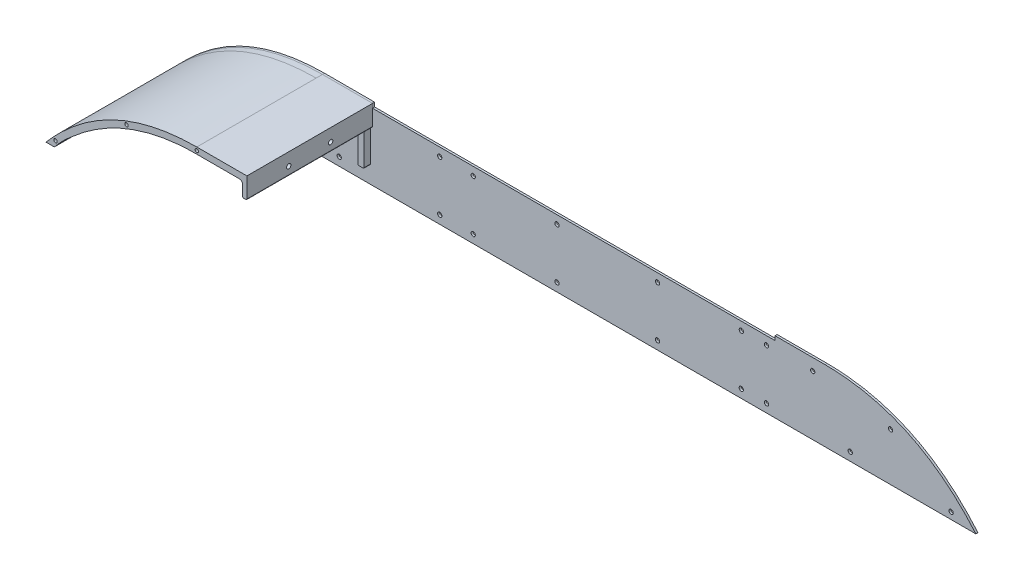
SolidWorks part; units mm, degrees
ref_plane "Front Plane" through (0, 0, 0) normal (0, 0, 1) x (1, 0, 0)
ref_plane "Top Plane" through (0, 0, 0) normal (0, 1, 0) x (1, 0, 0)
ref_plane "Right Plane" through (0, 0, 0) normal (1, 0, 0) x (0, 0, -1)
sketch "Sketch1" plane through (0, 0, 0) normal (0, 0, 1) x (1, 0, 0)
  line L0 (0, 0) -> (-304.8, 0)
  line L1 (0, 0) -> (609.6, 0)
  line L2 (0, 0) -> (0, 107.95) construction
  line L3 (0, 107.95) -> (609.6, 107.95)
  line L4 (609.6, 0) -> (609.6, 107.95) construction
  line L5 (609.6, 0) -> (914.4, 0)
  line L6 (304.8, -1000) -> (304.8, 49000) construction
  line L7 (0, 107.95) -> (-76.2, 107.95)
  line L8 (609.6, 107.95) -> (685.8, 107.95)
  spline S0 degree 2 poles (-304.8, 0) (-213.404, 107.36) (-76.2, 107.95) knots 0 0 0 1 1 1
  spline S1 degree 2 poles (914.4, 0) (823.004, 107.36) (685.8, 107.95) knots 0 0 0 1 1 1
  point P11 (304.8, 0)
  dimension "D1" = 609.6
  dimension "D2" = 107.95
  dimension "D3" = 304.8
  dimension "D4" = 76.2
extrude "Boss-Extrude1" add sketch "Sketch1" along normal blind 3.175
sketch "Sketch2" plane through (0, 0, 3.175) normal (0, 0, 1) x (1, 0, 0)
  line L8 (685.8, 107.95) -> (-76.2, 107.95) construction
  line L11 (0, 107.95) -> (609.6, 107.95)
  line L12 (0, 107.95) -> (0, 101.6) construction
  line L13 (0, 101.6) -> (609.6, 101.6)
  line L14 (609.6, 107.95) -> (609.6, 101.6) construction
  line L15 (-0.254, 107.95) -> (-0.254, 101.6)
  line L16 (609.854, 107.95) -> (609.854, 101.6)
  line L19 (609.6, 107.95) -> (609.854, 107.95)
  line L20 (609.6, 101.6) -> (609.854, 101.6)
  line L21 (-0.254, 107.95) -> (0, 107.95)
  line L22 (-0.254, 101.6) -> (0, 101.6)
  dimension "D1" = 609.6
  dimension "D2" = 6.35
  dimension "D3" = 0.254
  dimension "D4" = 0.254
extrude "Cut-Extrude1" cut sketch "Sketch2" against normal through all
sketch "Sketch3" plane through (0, 0, 3.175) normal (0, 0, 1) x (1, 0, 0)
  line L5 (-76.0908, 82.5502) -> (-76.2, 107.95) construction
  line L6 (685.8, 107.95) -> (609.854, 107.95)
  line L7 (609.854, 107.95) -> (609.854, 101.6)
  line L8 (609.854, 101.6) -> (-0.254, 101.6)
  line L9 (-0.254, 101.6) -> (-0.254, 107.95)
  line L10 (-0.254, 107.95) -> (-76.2, 107.95)
  line L11 (-304.8, 0) -> (914.4, 0)
  line L19 (-304.8, 0) -> (-254.508, 0)
  line L20 (-304.8, 0) -> (914.4, 0) construction
  line L21 (-254.508, 0) -> (-254.508, 15.3448)
  line L22 (-76.2, 107.95) -> (-0.254, 107.95)
  line L23 (-0.254, 107.95) -> (-0.254, 76.2)
  line L24 (-0.254, 76.2) -> (-6.604, 76.2)
  line L25 (-6.604, 76.2) -> (-6.604, 82.5502)
  line L26 (-6.604, 82.5502) -> (-76.0908, 82.5502)
  parabola Q2 (-76.2, 107.95) -> (-304.8, 0) focus (-138.8032, -41.5009) apex (-192.9562, 84.7198)
  parabola Q3 (914.4, 0) -> (685.8, 107.95) focus (748.4032, -41.5009) apex (802.5562, 84.7198)
  parabola Q4 (-76.2, 107.95) -> (-304.8, 0) focus (-138.8032, -41.5009) apex (-192.9562, 84.7198)
  spline S0 degree 1 poles (-76.0908, 82.5502) (-285.4592, -16.4649) knots 0 0 1 1 construction
  spline S1 degree 3 poles (-76.0908, 82.5502) (-78.7263, 82.5389) (-84.0207, 82.4515) (-94.414, 82.0204) (-107.175, 81.0024) (-122.0857, 79.0209) (-140.2937, 75.5918) (-157.8592, 70.8643) (-175.9104, 64.4537) (-194.5198, 56.4637) (-212.4049, 46.7322) (-228.6865, 35.996) (-240.414, 27.3) (-249.9299, 19.4397) (-257.5609, 12.6326) (-263.3873, 7.1473) (-268.2089, 2.3627) (-271.8925, -1.4301) (-275.5622, -5.3024) (-280.0978, -10.2646) (-283.6939, -14.3913) (-285.4592, -16.4649) knots 0.497516 0.497516 0.497516 0.497516 0.497684 0.497853 0.498189 0.498526 0.498863 0.499456 0.499793 0.50021 0.500884 0.501221 0.501558 0.501878 0.502046 0.502231 0.502399 0.502483 0.502568 0.502737 0.502905 0.502905 0.502905 0.502905 only from (-76.0908, 82.5502) to (-270.5007, 0) construction
  spline S2 degree 2 poles (-254.508, 15.3448) (-177.7983, 82.8932) (-76.0908, 82.5502) knots 0 0 0 1 1 1
  dimension "D2" = 31.75
  dimension "D3" = 6.35
  dimension "D5" = 50.292
  dimension "D1" = 0
  dimension "D4" = 25.4
extrude "Boss-Extrude2" add sketch "Sketch3" along normal blind 9.525
sketch "Sketch5" plane through (0, 0, 12.7) normal (0, 0, 1) x (1, 0, 0)
  line L7 (-304.8, 0) -> (-292.1, 0)
  line L8 (-76.0372, 98.4251) -> (-6.604, 98.4251)
  line L9 (-6.604, 98.4251) -> (-6.604, 82.5502)
  line L14 (-304.8, 0) -> (-254.508, 0)
  line L15 (-254.508, 0) -> (-254.508, 15.3448)
  line L16 (-76.0908, 82.5502) -> (-6.604, 82.5502)
  line L17 (-6.604, 82.5502) -> (-6.604, 76.2)
  line L18 (-6.604, 76.2) -> (-0.254, 76.2)
  line L19 (-0.254, 76.2) -> (-0.254, 107.95)
  line L20 (-0.254, 107.95) -> (-76.2, 107.95)
  line L24 (-6.604, 82.5502) -> (-6.604, 76.2)
  line L25 (-6.604, 76.2) -> (-0.254, 76.2)
  line L26 (-0.254, 76.2) -> (-0.254, 107.95)
  line L27 (-0.254, 107.95) -> (-76.2, 107.95)
  parabola Q4 (-76.2, 107.95) -> (-304.8, 0) focus (-138.8032, -41.5009) apex (-192.9562, 84.7198)
  parabola Q5 (-254.508, 15.3448) -> (-76.0908, 82.5502) focus (-126.3995, -51.2914) apex (-169.7975, 66.5726)
  parabola Q6 (-76.2, 107.95) -> (-304.8, 0) focus (-138.8032, -41.5009) apex (-192.9562, 84.7198)
  parabola Q7 (-254.508, 15.3448) -> (-76.0908, 82.5502) focus (-126.3995, -51.2914) apex (-169.7975, 66.5726) construction
  spline S0 degree 1 poles (-264.9993, 27.259) (-76.0372, 98.4251) knots 0 0 1 1 construction
  spline S1 degree 3 poles (-264.9993, 27.259) (-263.3249, 28.7335) (-259.9376, 31.6547) (-253.107, 37.2998) (-244.419, 44.0244) (-233.7687, 51.5472) (-219.2659, 60.8476) (-200.5783, 71.0931) (-177.2837, 81.1523) (-153.1553, 88.9561) (-132.3866, 93.5719) (-115.3933, 96.1333) (-102.4647, 97.4901) (-91.5371, 98.1519) (-82.7134, 98.4012) (-78.2591, 98.4326) (-76.0372, 98.4251) knots 0.497832 0.497832 0.497832 0.497832 0.497965 0.498098 0.498363 0.498629 0.498895 0.499427 0.499958 0.50049 0.501022 0.501287 0.501553 0.501819 0.501952 0.502085 0.502085 0.502085 0.502085
  spline S2 degree 2 poles (-264.9993, 27.259) (-280.0432, 15.0907) (-292.1, 0) knots 0 0 0 1 1 1
  dimension "D3" = 12.7
  dimension "D1" = 0
  dimension "D2" = 15.875
extrude "Boss-Extrude3" add sketch "Sketch5" along normal blind 180.975
sketch "Sketch6" plane through (0, 0, 12.7) normal (0, 0, 1) x (1, 0, 0)
  line L1 (-254.508, 0) -> (-226.4253, 0)
  line L2 (-254.508, 0) -> (-254.508, 28.575)
  line L3 (-254.508, 28.575) -> (-226.4253, 28.575)
  line L4 (-226.4253, 0) -> (-226.4253, 28.575)
  dimension "D1" = 28.575
extrude "Cut-Extrude2" cut sketch "Sketch6" against normal up to surface (9.525 mm away) up to face at (204.1979, 60.3971, 3.175)
sketch "Sketch7" plane through (0, 0, 12.7) normal (0, 0, 1) x (1, 0, 0)
  line L0 (-292.1, 0) -> (-254.508, 0) construction
  line L1 (-254.508, 0) -> (-254.508, 28.575) construction
  line L2 (-76.0651, 90.1702) -> (-9.6958, 90.1702) construction
  line L3 (-6.604, 98.4251) -> (-6.604, 76.2) construction
  circle A0 centre (-267.208, 10.16) radius 3.275
  circle A1 centre (-175.3658, 72.6223) radius 3.275
  circle A3 centre (-57.404, 90.1702) radius 3.275
  parabola Q0 (-238.3942, 28.575) -> (-76.0908, 82.5502) focus (-126.3995, -51.2914) apex (-169.7975, 66.5726) construction
  parabola Q1 (-238.3942, 28.575) -> (-76.0908, 82.5502) focus (-126.3995, -51.2914) apex (-169.7975, 66.5726) construction
  spline S0 degree 1 poles (-243.0182, 34.6317) (-76.0651, 90.1702) knots 0 0 1 1 construction
  spline S1 degree 3 poles (-243.0182, 34.6317) (-239.9935, 36.9409) (-233.8311, 41.4586) (-224.4638, 47.7679) (-214.9157, 53.6525) (-202.0674, 60.8581) (-190.551, 66.4075) (-178.8009, 71.3309) (-171.8366, 73.9914) (-159.5844, 78.2202) (-143.5556, 82.8056) (-125.3458, 86.3973) (-110.4698, 88.391) (-99.1613, 89.4468) (-89.6088, 89.961) (-81.8979, 90.1535) (-78.0064, 90.1767) (-76.0651, 90.1702) knots 0.498271 0.498271 0.498271 0.498271 0.49851 0.498748 0.498986 0.499225 0.499694 0.499813 0.500051 0.500178 0.500655 0.501131 0.50137 0.501608 0.501846 0.501966 0.502085 0.502085 0.502085 0.502085 construction
  dimension "D1" = 6.55
  dimension "D5" = 6.55
  dimension "D6" = 6.55
  dimension "D2" = 10.16
  dimension "D4" = 12.7
  dimension "D7" = 50.8
  dimension "D3" = 7.62
extrude "Cut-Extrude3" cut sketch "Sketch7" against normal through all
sketch "Sketch8" plane through (-0.254, 0, 0) normal (1, 0, 0) x (0, 0, -1)
  line L0 (-1151.3542, 88.9) -> (48848.6458, 88.9) construction
  line L1 (-193.675, 76.2) -> (-3.175, 76.2) construction
  line L2 (-3.175, 76.2) -> (-3.175, 101.6) construction
  circle A2 centre (-66.675, 88.9) radius 3.325
  circle A5 centre (-130.175, 88.9) radius 3.325
  dimension "D2" = 6.65
  dimension "D4" = 63.5
  dimension "D1" = 12.7
  dimension "D3" = 2
extrude "Cut-Extrude5" cut sketch "Sketch8" against normal up to surface (6.35 mm away) up to face at (-6.604, 85.7251, 69.85)
sketch "Sketch9" plane through (0, 0, 193.675) normal (0, 0, 1) x (1, 0, 0)
  circle A0 centre (-290.3708, 9.1426) radius 2.6
  circle A1 centre (-182.7594, 83.8165) radius 2.6
  circle A2 centre (-76.1798, 103.25) radius 2.6
  parabola Q0 (-76.2, 107.95) -> (-304.8, 0) focus (-138.8032, -41.5009) apex (-192.9562, 84.7198) construction
  parabola Q1 (-76.2, 107.95) -> (-304.8, 0) focus (-138.8032, -41.5009) apex (-192.9562, 84.7198) construction
  spline S0 degree 1 poles (-76.1798, 103.25) (-301.2212, -3.0467) knots 0 0 1 1 construction
  spline S1 degree 3 poles (-76.1798, 103.25) (-78.9851, 103.238) (-84.6167, 103.1451) (-95.7036, 102.6853) (-109.3519, 101.5971) (-125.3575, 99.4709) (-145.1456, 95.7451) (-161.7727, 91.2541) (-177.9517, 85.7316) (-188.5878, 81.5829) (-206.0869, 73.7491) (-227.5653, 62.0602) (-249.2337, 46.8941) (-265.8815, 33.1047) (-277.7275, 22.2059) (-286.3, 13.5161) (-292.1052, 7.2837) (-296.2196, 2.7435) (-299.3516, -0.8505) (-301.2212, -3.0467) knots 0.497516 0.497516 0.497516 0.497516 0.497684 0.497853 0.498189 0.498526 0.498863 0.499468 0.499636 0.499973 0.50021 0.500884 0.501558 0.501895 0.502231 0.502544 0.502628 0.502737 0.502905 0.502905 0.502905 0.502905 construction
  dimension "D2" = 5.2
  dimension "D3" = 5.2
  dimension "D4" = 5.2
  dimension "D1" = 4.7
extrude "Cut-Extrude6" cut sketch "Sketch9" against normal blind 12.7
sketch "Sketch11" plane through (-254.508, 0, 0) normal (1, 0, 0) x (0, 0, -1)
  line L0 (-3.175, 0) -> (-3.175, 28.575) construction
  line L1 (-12.7, 0) -> (-3.175, 0) construction
  circle A0 centre (-7.1374, 3.9751) radius 1.9
  circle A3 centre (-7.1374, 21.4251) radius 1.9
  dimension "D3" = 3.8
  dimension "D1" = 3.9624
  dimension "D2" = 3.9751
  dimension "D4" = 2
extrude "Boss-Extrude5" add sketch "Sketch11" along normal blind 10.16
sketch "Sketch14" plane through (0, 82.5502, 0) normal (0, -1, 0) x (1, 0, 0)
  line L5 (-76.0372, 12.7) -> (-6.604, 12.7) construction
  line L6 (-0.254, 3.175) -> (-12.954, 3.175)
  line L7 (-0.254, 3.175) -> (-0.254, 12.7)
  line L8 (-0.254, 12.7) -> (-12.954, 12.7)
  line L9 (-12.954, 3.175) -> (-12.954, 12.7)
  dimension "D1" = 12.7
extrude "Boss-Extrude8" add sketch "Sketch14" along normal offset from surface (57.1502 mm away) 25.4 up to face at (-48.3616, 0, 43.4975)
sketch "Sketch17" plane through (-0.254, 0, 0) normal (1, 0, 0) x (0, 0, -1)
  line L1 (-12.7, 76.2) -> (-3.175, 76.2)
  line L2 (-12.7, 76.2) -> (-12.7, 25.4)
  line L3 (-12.7, 25.4) -> (-3.175, 25.4)
  line L4 (-3.175, 76.2) -> (-3.175, 25.4)
extrude "Cut-Extrude9" cut sketch "Sketch17" against normal blind 3.175
fillet "Fillet1" radius 5 1 edges at (-6.604, 98.4251, 103.1875)
fillet "Fillet2" radius 2 2 edges at (-238.3942, 28.575, 7.9375) (-254.508, 28.575, 7.9375)
fillet "Fillet3" radius 1 1 edges at (-292.1, 0, 103.1875)
fillet "Fillet8" radius 5 1 edges at (-12.954, 82.5502, 7.9375)
fillet "Fillet9" radius 1.5 4 edges at (-0.254, 76.2, 98.425) (-6.604, 76.2, 103.1875) (-12.954, 25.4, 7.9375) (-3.429, 25.4, 7.9375)
fillet "Fillet10" radius 1.5 1 edges at (-3.429, 76.2, 7.9375)
sketch "Sketch18" plane through (0, 0, 0) normal (0, 0, -1) x (-1, 0, 0)
  line L0 (-1304.4923, 12.7) -> (48695.5077, 12.7) construction
  line L1 (304.8, 0) -> (-914.4, 0) construction
  line L2 (0.254, 77.7) -> (0.254, 107.95) construction
  line L3 (-1393.9168, 88.9) -> (48606.0832, 88.9) construction
  line L4 (0.254, 101.6) -> (-609.854, 101.6) construction
  line L5 (-609.854, 101.6) -> (-609.854, 107.95) construction
  line L6 (-584.2, 101.6) -> (-584.2, 0) construction
  line L7 (-127, 101.6) -> (-127, 0) construction
  circle A0 centre (50.8, 12.7) radius 3.275
  circle A1 centre (-101.6, 12.7) radius 3.275
  circle A2 centre (-101.6, 88.9) radius 3.275
  circle A3 centre (-558.8, 88.9) radius 3.275
  circle A4 centre (-152.4, 88.9) radius 3.275
  circle A5 centre (-596.9, 88.9) radius 3.275
  circle A6 centre (-596.9, 12.7) radius 3.275
  circle A7 centre (-558.8, 12.7) radius 3.275
  circle A8 centre (-152.4, 12.7) radius 3.275
  circle A9 centre (-723.9, 12.7) radius 3.275
  circle A11 centre (-431.8, 88.9) radius 3.275
  circle A12 centre (-431.8, 12.7) radius 3.275
  circle A13 centre (-279.4, 12.7) radius 3.275
  circle A14 centre (-279.4, 88.9) radius 3.275
  dimension "D2" = 6.55
  dimension "D4" = 6.55
  dimension "D6" = 6.55
  dimension "D7" = 6.55
  dimension "D15" = 2
  dimension "D1" = 12.7
  dimension "D3" = 50.8
  dimension "D5" = 101.854
  dimension "D8" = 12.7
  dimension "D9" = 12.954
  dimension "D10" = 25.654
  dimension "D11" = 127.254
  dimension "D12" = 127
  dimension "D13" = 25.4
  dimension "D14" = 25.4
  dimension "D16" = 2
extrude "Cut-Extrude10" cut sketch "Sketch18" against normal blind 12.7
ref_plane "midplane" through (304.8, 0, 0) normal (1, 0, 0) x (0, 0, -1)
mirror "Mirror1" about plane through (304.8, 0, 0) normal (1, 0, 0) of "Cut-Extrude3"
ref_plane "Plane2" through (584.2, 0, 0) normal (-1, 0, 0) x (0, 0, 1)
split "Split1" bodies to split 126 resulting bodies 128 129 split by face at (873.533, 10.16, 3.175)
